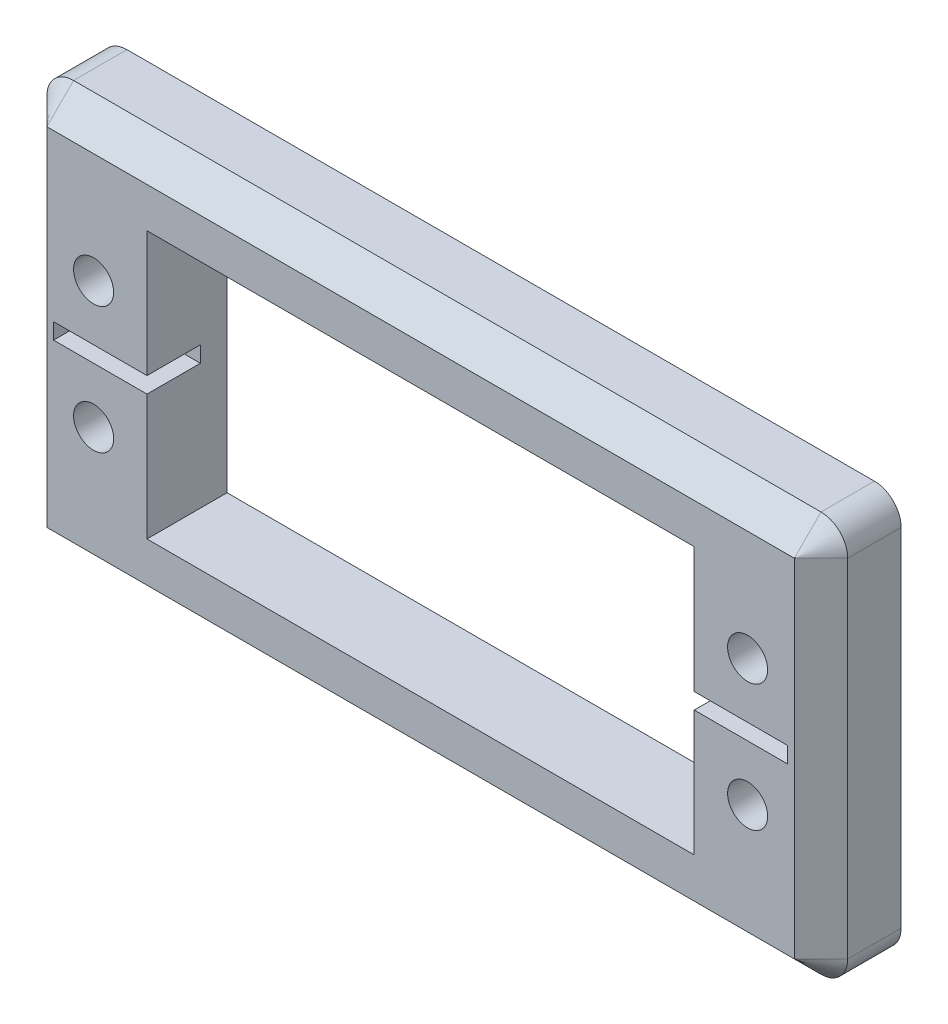
SolidWorks part; units mm, degrees
ref_plane "Front Plane" through (0, 0, 0) normal (0, 0, 1) x (1, 0, 0)
ref_plane "Top Plane" through (0, 0, 0) normal (0, 1, 0) x (1, 0, 0)
ref_plane "Right Plane" through (0, 0, 0) normal (1, 0, 0) x (0, 0, -1)
sketch "Sketch1" plane through (0, 0, 0) normal (0, 0, 1) x (1, 0, 0)
  line L1 (-30, -15) -> (30, -15)
  line L2 (-30, -15) -> (-30, 15)
  line L3 (-30, 15) -> (30, 15)
  line L4 (30, -15) -> (30, 15)
  line L5 (-30, -15) -> (30, 15) construction
  line L6 (-30, 15) -> (30, -15) construction
  point P0 (0, 0)
  dimension "D1" = 60
  dimension "D2" = 30
extrude "Boss-Extrude1" add sketch "Sketch1" along normal blind 10
sketch "Sketch2" plane through (0, 0, 10) normal (0, 0, 1) x (1, 0, 0)
  line L1 (-20.5, -10) -> (20.5, -10)
  line L2 (-20.5, -10) -> (-20.5, 10)
  line L3 (-20.5, 10) -> (20.5, 10)
  line L4 (20.5, -10) -> (20.5, 10)
  line L5 (-20.5, -10) -> (20.5, 10) construction
  line L6 (-20.5, 10) -> (20.5, -10) construction
  point P0 (0, 0)
  dimension "D1" = 41
  dimension "D2" = 20
extrude "Cut-Extrude1" cut sketch "Sketch2" against normal blind 10
sketch "Sketch4" plane through (0, 0, 10) normal (0, 0, 1) x (1, 0, 0)
  line L1 (-27.5, -10) -> (27.5, -10)
  line L2 (-27.5, -10) -> (-27.5, 10)
  line L3 (-27.5, 10) -> (27.5, 10)
  line L4 (27.5, -10) -> (27.5, 10)
  line L5 (-27.5, -10) -> (27.5, 10) construction
  line L6 (-27.5, 10) -> (27.5, -10) construction
  point P0 (0, 0)
  dimension "D1" = 55
  dimension "D2" = 20
sketch "Sketch3" plane through (0, 0, 10) normal (0, 0, 1) x (1, 0, 0)
  line L0 (0, 0) -> (33.6124, 0) construction
  line L1 (33.6124, 0) -> (-41.1923, 0) construction
  line L2 (-20.5, 10) -> (-20.5, -10) construction
  line L3 (-13.5, 0.6) -> (-27.5, 0.6)
  line L4 (-13.5, 0.6) -> (-13.5, -0.6)
  line L5 (-13.5, -0.6) -> (-27.5, -0.6)
  line L6 (-27.5, 0.6) -> (-27.5, -0.6)
  line L7 (-13.5, 0.6) -> (-27.5, -0.6) construction
  line L8 (-13.5, -0.6) -> (-27.5, 0.6) construction
  line L9 (-27.5, -10) -> (-27.5, 10) construction
  line L10 (-24.5, 4.75) -> (-24.5, -13.2201) construction
  line L11 (0, 9.0017) -> (0, -13.0942) construction
  line L12 (24.5, 4.75) -> (24.5, -13.2201) construction
  line L13 (13.5, -0.6) -> (27.5, 0.6) construction
  line L14 (13.5, 0.6) -> (27.5, -0.6) construction
  line L15 (-33.6124, 0) -> (41.1923, 0) construction
  line L16 (27.5, 0.6) -> (27.5, -0.6)
  line L17 (13.5, -0.6) -> (27.5, -0.6)
  line L18 (13.5, 0.6) -> (13.5, -0.6)
  line L19 (13.5, 0.6) -> (27.5, 0.6)
  line L20 (-27.5, 10) -> (27.5, 10) construction
  circle A0 centre (-24.5, 4.75) radius 1.5
  circle A2 centre (-24.5, -4.75) radius 1.5
  circle A3 centre (24.5, -4.75) radius 1.5
  circle A4 centre (24.5, 4.75) radius 1.5
  point P3 (-20.5, 0)
  point P30 (20.5, 0)
  dimension "D2" = 3
  dimension "D3" = 3
  dimension "D1" = 1.2
  dimension "D4" = 5.25
extrude "Cut-Extrude2" cut sketch "Sketch3" against normal blind 4
fillet "Fillet1" radius 2 4 edges at (30, 15, 5) (30, -15, 5) (-30, -15, 5) (-30, 15, 5) tangent propagation no
chamfer "Chamfer1" distance 2 angle 45 8 edges at (0, -15, 10) (29.4142, -14.4142, 10) (-29.4142, -14.4142, 10) (30, 0, 10) (-30, 0, 10) (29.4142, 14.4142, 10) (-29.4142, 14.4142, 10) (0, 15, 10)
sketch "Sketch5" plane through (0, 0, 0) normal (0, 0, -1) x (-1, 0, 0)
  line L1 (-110.7159, 60.173) -> (34.7929, 60.173)
  line L2 (-110.7159, 60.173) -> (-110.7159, -18.8565)
  line L3 (-110.7159, -18.8565) -> (34.7929, -18.8565)
  line L4 (34.7929, 60.173) -> (34.7929, -18.8565)
  line L5 (-110.7159, 60.173) -> (34.7929, -18.8565) construction
  line L6 (-110.7159, -18.8565) -> (34.7929, 60.173) construction
  point P0 (-37.9615, 20.6583)
extrude "Cut-Extrude3" cut sketch "Sketch5" against normal blind 4
